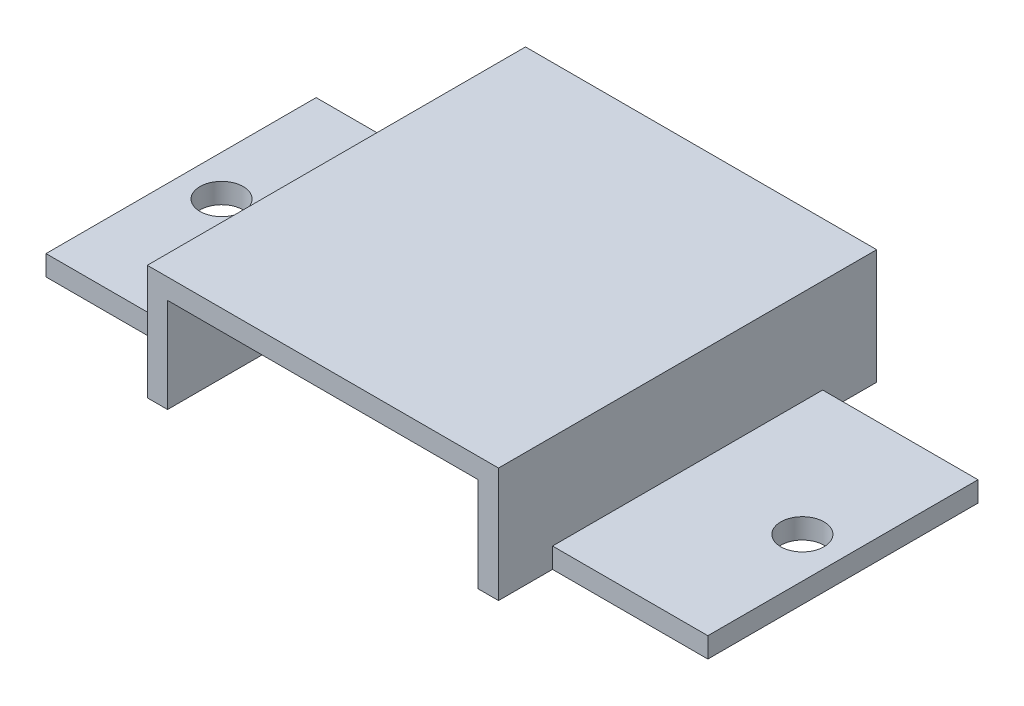
SolidWorks part; units mm, degrees
material "PEI"
ref_plane "Front Plane" through (0, 0, 0) normal (0, 0, 1) x (1, 0, 0)
ref_plane "Top Plane" through (0, 0, 0) normal (0, 1, 0) x (1, 0, 0)
ref_plane "Right Plane" through (0, 0, 0) normal (1, 0, 0) x (0, 0, -1)
sketch "Sketch1" plane through (0, 0, 0) normal (0, 0, 1) x (1, 0, 0)
  line L0 (0, 8.5) -> (0, -9.3416) construction
  line L1 (0, 0) -> (-24.5, 0)
  line L2 (-24.5, 0) -> (-24.5, 1.5)
  line L3 (-24.5, 1.5) -> (-13, 1.5)
  line L4 (-13, 1.5) -> (-13, 8.5)
  line L5 (-13, 8.5) -> (0, 8.5)
  line L6 (0, 8.5) -> (0, 7)
  line L7 (0, 7) -> (-11.5, 7)
  line L8 (-11.5, 7) -> (-11.5, 0)
  dimension "D1" = 1.5
  dimension "D2" = 1.5
  dimension "D3" = 11.5
  dimension "D4" = 24.5
  dimension "D5" = 1.5
  dimension "D6" = 7
extrude "Boss-Extrude1" add sketch "Sketch1" along normal mid plane 28 contours L8 L7 L6 L5 L4 L3 L2 L1 region at (-12.25, 4.25, 0)
mirror "Mirror1" about plane through (0, 0, 0) normal (1, 0, 0) of "Boss-Extrude1"
sketch "Sketch2" plane through (0, 8.5, 0) normal (0, 1, 0) x (1, 0, 0)
  line L0 (24.5, 14) -> (13, 14) construction
  line L1 (13, 14) -> (13, -14) construction
  line L2 (13, -14) -> (24.5, -14) construction
  line L3 (24.5, -14) -> (24.5, 14) construction
  line L4 (13, 14) -> (-13, 14)
  line L5 (-13, 14) -> (-13, -14)
  line L6 (-13, -14) -> (13, -14)
  line L7 (13, -14) -> (13, 14)
  line L8 (13, 14) -> (-13, 14)
  line L9 (-13, 14) -> (-13, -14)
  line L10 (-13, -14) -> (13, -14)
  line L11 (13, -14) -> (13, 14)
  line L12 (-13, 14) -> (-24.5, 14) construction
  line L13 (-24.5, 14) -> (-24.5, -14) construction
  line L14 (-24.5, -14) -> (-13, -14) construction
  line L15 (-13, -14) -> (-13, 14) construction
  line L16 (24.5, 14) -> (13, 14)
  line L17 (13, 14) -> (13, -14)
  line L18 (13, -14) -> (24.5, -14)
  line L19 (24.5, -14) -> (24.5, 14)
  line L20 (-13, 14) -> (-24.5, 14)
  line L21 (-24.5, 14) -> (-24.5, -14)
  line L22 (-24.5, -14) -> (-13, -14)
  line L23 (-13, -14) -> (-13, 14)
  line L24 (-13, 10) -> (-24.5, 10)
  line L25 (-13, -10) -> (-24.5, -10)
  line L26 (0, 0) -> (0, 14)
  line L27 (13, -10) -> (24.5, -10)
  line L28 (13, 10) -> (24.5, 10)
  line M10 (-13, 14) -> (-13, -14)
  line M12 (13, -14) -> (13, 14)
  dimension "D2" = 4
  dimension "D3" = 4
  dimension "D1" = 0
extrude "Cut-Extrude1" cut sketch "Sketch2" against normal through all contours L24 L20 L21 M10 | L25 L21 L22 M10 | L28 L19 L16 M12 | L27 L18 L19 M12 region at (18.75, 8.5, -12) region at (-18.75, 8.5, -12) region at (18.75, 8.5, 12) region at (-18.75, 8.5, 12)
sketch "Sketch4" plane through (0, 1.5, 0) normal (0, 1, 0) x (1, 0, 0)
  line L0 (24.5, 0) -> (21.5, 0)
  line L1 (0, 0) -> (0, -15.3594)
  line L4 (24.5, -10) -> (24.5, 10)
  line L5 (24.5, 10) -> (13, 10)
  line L6 (13, 10) -> (13, -10)
  line L7 (13, -10) -> (24.5, -10)
  line L8 (24.5, -10) -> (24.5, 10)
  line L9 (24.5, 10) -> (13, 10)
  line L10 (13, 10) -> (13, -10)
  line L11 (13, -10) -> (24.5, -10)
  circle A0 centre (21.5, 0) radius 1.6
  circle A1 centre (-21.5, 0) radius 1.6
  dimension "D3" = 3.2
  dimension "D2" = 3
  dimension "D1" = 0
extrude "Cut-Extrude2" cut sketch "Sketch4" against normal through all contours A0 | A1 region at (19.9453, 1.5, 0) region at (-21.5, 1.5, 0)
